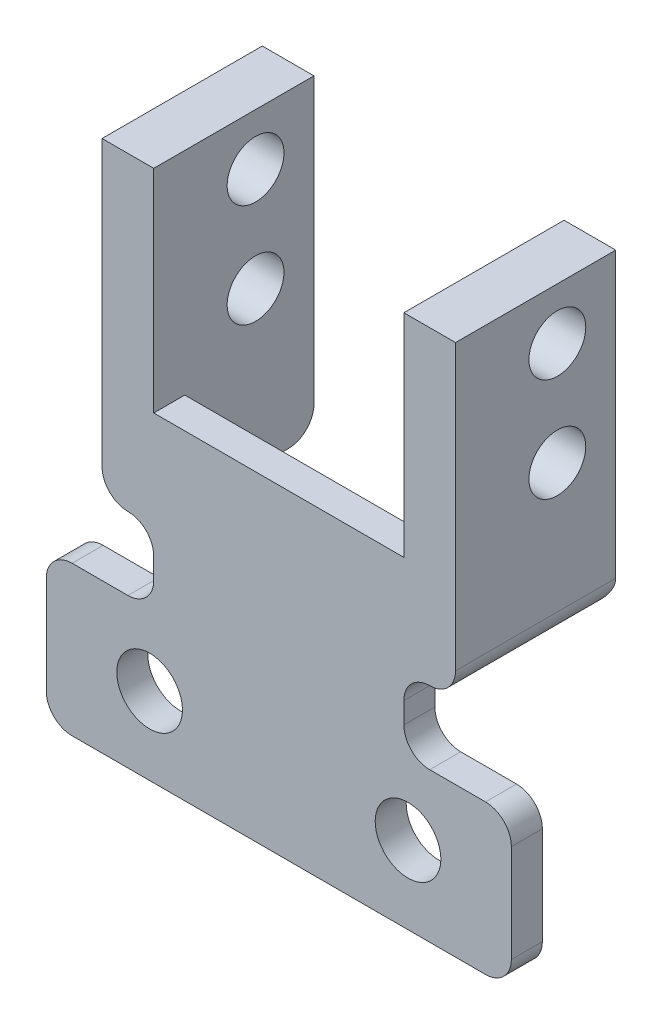
SolidWorks part; units mm, degrees
ref_plane "Front Plane" through (0, 0, 0) normal (0, 0, 1) x (1, 0, 0)
ref_plane "Top Plane" through (0, 0, 0) normal (0, 1, 0) x (1, 0, 0)
ref_plane "Right Plane" through (0, 0, 0) normal (1, 0, 0) x (0, 0, -1)
sketch "Sketch1" plane through (0, 0, 0) normal (0, 0, 1) x (1, 0, 0)
  line L1 (-8.5113, 5.428) -> (36.4887, 5.428)
  line L2 (-8.5113, 5.428) -> (-8.5113, -9.032)
  line L3 (-8.5113, -9.032) -> (36.4887, -9.032)
  line L4 (36.4887, 5.428) -> (36.4887, -9.032)
  dimension "D1" = 45
  dimension "D2" = 14.46
extrude "Boss-Extrude1" add sketch "Sketch1" along normal blind 3
sketch "Sketch2" plane through (0, 0, 0) normal (0, 0, -1) x (-1, 0, 0)
  line L0 (8.5113, -9.032) -> (-36.4887, -9.032) construction
  line L1 (-36.4887, 5.428) -> (8.5113, 5.428) construction
  point P0 (-26.4887, -1.532)
  point P1 (-1.4887, -1.532)
  point P4 (-13.9887, -9.032)
  dimension "D1" = 25
  dimension "D2" = 12.5
  dimension "D3" = 6.96
hole_wizard "1/4 (0.25) Diameter Hole1" positions "Sketch3" profile "Sketch4" hole size "1/4" standard "ANSI Inch" end condition through all
sketch "Sketch3" plane through (0, 0, 0) normal (0, 0, -1) x (-1, 0, 0)
  point P0 (-26.4887, -1.532)
  point P3 (-1.4887, -1.532)
sketch "Sketch4" plane through (26.4887, -1.532, 0) normal (1, 0, 0) x (0, 1, 0)
  line L0 (0, 0) -> (0, 3)
  line L1 (0, 3) -> (3.175, 3)
  line L2 (3.175, 3) -> (3.175, 0)
  line L5 (3.175, 0) -> (0, 0)
  line L11 (0, -6.35) -> (0, 107.95) construction
  dimension "Thru Hole Dia." = 6.35
  dimension "Thru Hole Depth" = 3
sketch "Sketch5" plane through (0, 0, 0) normal (0, 0, -1) x (-1, 0, 0)
  line L0 (-36.4887, 5.428) -> (8.5113, 5.428) construction
  line L1 (-26.0887, 5.428) -> (-1.8887, 5.428)
  line L2 (-26.0887, 5.428) -> (-26.0887, 42.468)
  line L3 (-26.0887, 42.468) -> (-1.8887, 42.468)
  line L4 (-1.8887, 5.428) -> (-1.8887, 42.468)
  line L5 (8.5113, -9.032) -> (-36.4887, -9.032) construction
  point P6 (-13.9887, 42.468)
  point P9 (-13.9887, -9.032)
  dimension "D1" = 24.2
  dimension "D2" = 0
  dimension "D3" = 44
extrude "Boss-Extrude2" add sketch "Sketch5" against normal blind 3
sketch "Sketch6" plane through (1.8887, 0, 0) normal (-1, 0, 0) x (0, 0, 1)
  line L0 (0, 5.428) -> (0, 42.468) construction
  line L1 (3, 42.468) -> (-12.5, 42.468)
  line L2 (3, 42.468) -> (3, 12.468)
  line L3 (3, 12.468) -> (-12.5, 12.468)
  line L4 (-12.5, 42.468) -> (-12.5, 12.468)
  dimension "D1" = 30
  dimension "D2" = 12.5
extrude "Boss-Extrude3" add sketch "Sketch6" along normal blind 5
sketch "Sketch7" plane through (-3.1113, 0, 0) normal (-1, 0, 0) x (0, 0, 1)
  line L1 (-12.5, 42.468) -> (3, 42.468)
  line L2 (-12.5, 42.468) -> (-12.5, 12.468)
  line L3 (-12.5, 12.468) -> (3, 12.468)
  line L4 (3, 42.468) -> (3, 12.468)
extrude "Boss-Extrude4" add sketch "Sketch7" against normal blind 5 from surface starting at face at (26.0887, 23.948, 1.5)
sketch "Sketch8" plane through (-3.1113, 0, 0) normal (-1, 0, 0) x (0, 0, 1)
  line L2 (3, 42.468) -> (-12.5, 42.468) construction
  line L3 (3, 12.468) -> (3, 42.468) construction
  point P0 (-6.85, 27.468)
  point P1 (-6.85, 37.468)
  dimension "D1" = 9.85
  dimension "D2" = 0
  dimension "D3" = 5
  dimension "D4" = 10
sketch "Sketch12" plane through (0, 0, 0) normal (0, 0, -1) x (-1, 0, 0)
  line L0 (-1.8887, 12.468) -> (-1.8887, 42.468) construction
  line L1 (-26.0887, 42.468) -> (-1.8887, 42.468)
  line L2 (-26.0887, 42.468) -> (-26.0887, 21.968)
  line L3 (-26.0887, 21.968) -> (-1.8887, 21.968)
  line L4 (-1.8887, 42.468) -> (-1.8887, 21.968)
  dimension "D1" = 20.5
extrude "Cut-Extrude1" cut sketch "Sketch12" against normal up to surface (3 mm away) up to face at (23.3137, -1.532, 3)
hole_wizard "M5 Clearance Hole1" positions "Sketch9" profile "Sketch10" hole size "M5" standard "ANSI Metric" end condition through all
sketch "Sketch9" plane through (-3.1113, 0, 0) normal (-1, 0, 0) x (0, 0, 1)
  point P0 (-6.85, 37.468)
  point P3 (-6.85, 27.468)
sketch "Sketch10" plane through (-3.1113, 37.468, -6.85) normal (0, 1, 0) x (0, 0, 1)
  line L0 (0, 0) -> (0, 39.6)
  line L1 (0, 39.6) -> (2.75, 39.6)
  line L2 (2.75, 39.6) -> (2.75, 0)
  line L5 (2.75, 0) -> (0, 0)
  line L11 (0, -6.35) -> (0, 107.95) construction
  dimension "Thru Hole Dia." = 5.5
  dimension "Thru Hole Depth" = 39.6
fillet "Fillet3" radius 2.5 4 edges at (36.4887, -9.032, 1.5) (36.4887, 5.428, 1.5) (-8.5113, -9.032, 1.5) (-8.5113, 5.428, 1.5)
fillet "Fillet4" radius 2.5 8 edges at (1.8887, 5.428, 1.5) (26.0887, 5.428, 1.5) (26.0887, 12.468, 1.5) (1.8887, 12.468, 1.5) (31.0887, 12.468, -4.75) (-3.1113, 12.468, -4.75) (28.5887, 12.468, -12.5) (-0.6113, 12.468, -12.5)
equation "\"D3@Sketch5\"=15+20 + 9"
